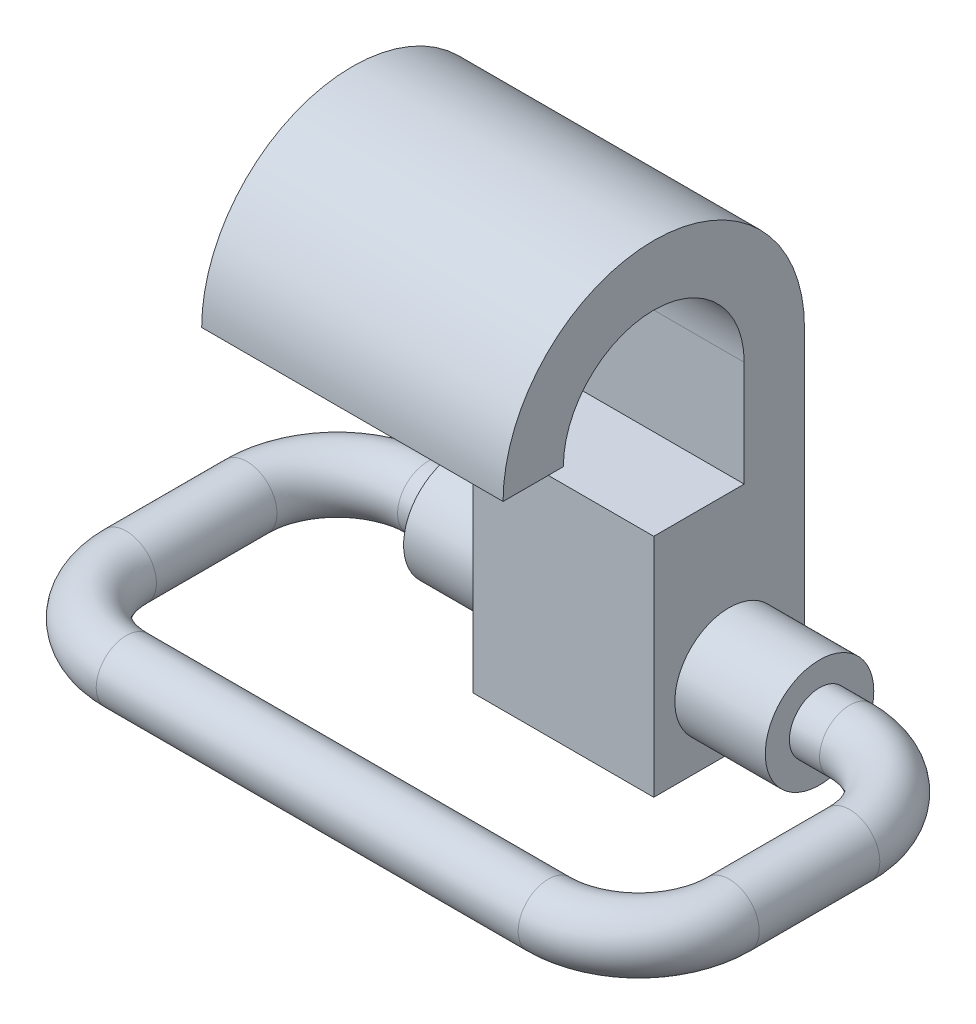
SolidWorks part; units mm, degrees
ref_plane "Plano frontal" through (0, 0, 0) normal (0, 0, 1) x (1, 0, 0)
ref_plane "Plano superior" through (0, 0, 0) normal (0, 1, 0) x (1, 0, 0)
ref_plane "Plano direito" through (0, 0, 0) normal (1, 0, 0) x (0, 0, -1)
sketch "Esboço1" plane through (0, 0, 0) normal (1, 0, 0) x (0, 0, -1)
  line L0 (-250, -375) -> (250, -375)
  line L1 (-250, -375) -> (-250, 375)
  line L2 (250, -375) -> (250, 375)
  line L3 (-250, 375) -> (250, 375)
  line L4 (-250, -375) -> (250, 375) construction
  line L5 (250, -375) -> (-250, 375) construction
  line L6 (250, -375) -> (0, -375) construction
  line L7 (0, -375) -> (0, -135) construction
  line L8 (250, 375) -> (50, 375) construction
  line L9 (50, 375) -> (250, 375)
  line L10 (50, 375) -> (50, 725)
  line L11 (250, 375) -> (250, 725)
  line L12 (50, 725) -> (250, 725)
  circle A0 centre (0, -135) radius 180
  circle A1 centre (0, -135) radius 100
  point P1 (0, 0)
  dimension "D4" = 360
  dimension "D5" = 200
  dimension "D1" = 750
  dimension "D2" = 500
  dimension "D3" = 240
  dimension "D6" = 200
  dimension "D7" = 350
extrude "Ressalto-extrusão2" add sketch "Esboço1" along normal blind 700 contours A1 region at (0, -135, 0)
extrude "Ressalto-extrusão6" add sketch "Esboço1<9>" along normal blind 600 contours A0 A1 region at (0, -135, 174.9088)
sketch "Esboço1<9>" plane through (0, 0, 0) normal (1, 0, 0) x (0, 0, -1) same geometry as "Esboço1"
extrude "Ressalto-extrusão7" add sketch "Esboço1<10>" along normal blind 300 contours L3 L1 L0 L2 A0 region at (0, 50.2954, 0)
sketch "Esboço1<10>" plane through (0, 0, 0) normal (1, 0, 0) x (0, 0, -1) same geometry as "Esboço1"
sketch "Esboço3" plane through (0, 375, 0) normal (0, 1, 0) x (1, 0, 0)
  line L0 (0, 250) -> (0, 50) construction
  line L1 (0, -250) -> (0, 250) construction
  line L3 (0, 50) -> (300, 50)
  line L4 (0, 50) -> (0, 250)
  line L5 (0, 250) -> (300, 250)
  line L6 (300, 50) -> (300, 250)
  dimension "D1" = 200
extrude "Ressalto-extrusão8" add sketch "Esboço3" along normal blind 350
sketch "Esboço5" plane through (300, 0, 0) normal (1, 0, 0) x (0, 0, -1)
  line L0 (50, 725) -> (-250, 725) construction
  line L1 (-750, 725) -> (-550, 725)
  line L2 (250, 725) -> (50, 725)
  arc A0 (50, 725) -> (-550, 725) centre (-250, 725) ccw
  arc A1 (250, 725) -> (-750, 725) centre (-250, 725) ccw
  dimension "D1" = 300
sketch "Esboço6" plane through (0, 0, 0) normal (-1, 0, 0) x (0, 0, 1)
  line L0 (-50, 725) -> (250, 725) construction
  line L1 (-250, 725) -> (-50, 725) construction
  line L2 (-50, 725) -> (-50, 375) construction
  dimension "D1" = 300
extrude "Ressalto-extrusão9" add sketch "Esboço5" against normal blind 300 contours A1 L1 A0 L2
sketch3d "3DSketch1" plane through (0, 0, 0) normal (0, 0, 1) x (1, 0, 0)
  dimension "D1" = 240
sketch "Esboço7" plane through (700, 0, 0) normal (1, 0, 0) x (0, 0, -1)
  point P0 (0, -135)
sketch "Esboço8" plane through (0, -135, 0) normal (0, -1, 0) x (-1, 0, 0)
  line L0 (-700, 0) -> (-700, -300) construction
  arc A0 (-700, 0) -> (-1000, -300) centre (-700, -300) ccw
  dimension "D1" = 300
sketch "Esboço9" plane through (700, 0, 0) normal (1, 0, 0) x (0, 0, -1)
  circle A0 centre (0, -135) radius 100
sweep "Varredura1" add profiles "Esboço9" path "Esboço8"
sketch "Esboço10" plane through (0, 0, 300) normal (0, 0, 1) x (1, 0, 0)
  circle A0 centre (1000, -135) radius 100
extrude "Ressalto-extrusão10" add sketch "Esboço10" along normal blind 400 contours A0
sketch "Esboço13" plane through (0, 0, 700) normal (0, 0, 1) x (1, 0, 0)
  point P0 (1000, -135)
sketch "Esboço14" plane through (0, -135, 0) normal (0, -1, 0) x (-1, 0, 0)
  line L0 (-1000, -700) -> (-700, -700) construction
  line L1 (-1100, -700) -> (-900, -700) construction
  arc A0 (-1000, -700) -> (-700, -1000) centre (-700, -700) ccw
  dimension "D1" = 300
sketch "Esboço15" plane through (0, 0, 700) normal (0, 0, 1) x (1, 0, 0)
  circle A0 centre (1000, -135) radius 100
sweep "Varredura2" add profiles "Esboço15" path "Esboço14"
sketch "Esboço17" plane through (700, 0, 0) normal (-1, 0, 0) x (0, 0, 1)
  circle A0 centre (1000, -135) radius 100
sketch "Esboço19" plane through (700, 0, 0) normal (-1, 0, 0) x (0, 0, 1)
extrude "Ressalto-extrusão11" add sketch "Esboço17" along normal blind 700
mirror "Espelhar1" of "Ressalto-extrusão11"
mirror "Espelhar2" of "Varredura2"
mirror "Espelhar3" of "Ressalto-extrusão10"
mirror "Espelhar4" of "Varredura1"
mirror "Espelhar5" of "Ressalto-extrusão2"
mirror "Espelhar6" of "Ressalto-extrusão6"
mirror "Espelhar7" of "Ressalto-extrusão9"
mirror "Espelhar8" about plane through (300, 0, 0) normal (1, 0, 0) of "Ressalto-extrusão2"
ref_plane "Plano1" through (0, -375, 250) normal (0, 1, 0) x (1, 0, 0)
sketch "Esboço21" plane through (0, 0, 0) normal (-1, 0, 0) x (0, 0, 1)
  line L0 (250, -375) -> (-250, -375) construction
  line L1 (250, 375) -> (-250, 375)
  line L2 (250, 375) -> (250, -375)
  line L3 (250, -375) -> (-250, -375)
  line L4 (-250, 375) -> (-250, -375)
  line L5 (-250, -375) -> (-250, 725) construction
extrude "Ressalto-extrusão12" add sketch "Esboço21" along normal blind 300
sketch "Esboço22" plane through (0, 0, 0) normal (-1, 0, 0) x (0, 0, 1)
  line L1 (-250, 725) -> (-50, 725)
  line L2 (-250, 725) -> (-250, 375)
  line L3 (-250, 375) -> (-50, 375)
  line L4 (-50, 725) -> (-50, 375)
extrude "Ressalto-extrusão13" add sketch "Esboço22" along normal blind 300
sketch "Esboço26" plane through (-300, 0, 0) normal (-1, 0, 0) x (0, 0, 1)
  line L0 (-250, 725) -> (-50, 725)
  line L1 (550, 725) -> (750, 725)
  arc A0 (750, 725) -> (-250, 725) centre (250, 725) ccw
  arc A1 (750, 725) -> (-250, 725) centre (250, 725) ccw construction
  arc A2 (550, 725) -> (-50, 725) centre (250, 725) ccw
  arc A3 (550, 725) -> (-50, 725) centre (250, 725) ccw construction
extrude "Ressalto-extrusão14" add sketch "Esboço26" along normal blind 400
sketch "Esboço27" plane through (-700, 0, 0) normal (-1, 0, 0) x (0, 0, 1)
  line L0 (-250, 725) -> (-50, 725) construction
  line L1 (-122.3909, 940) -> (-183.0127, 975)
  line L2 (-180, 725) -> (-250, 725)
  arc A0 (-250, 725) -> (-183.0127, 975) centre (250, 725) cw
  arc A1 (750, 725) -> (-250, 725) centre (250, 725) ccw construction
  arc A2 (-180, 725) -> (-122.3909, 940) centre (250, 725) cw
  point P0 (250, 725)
